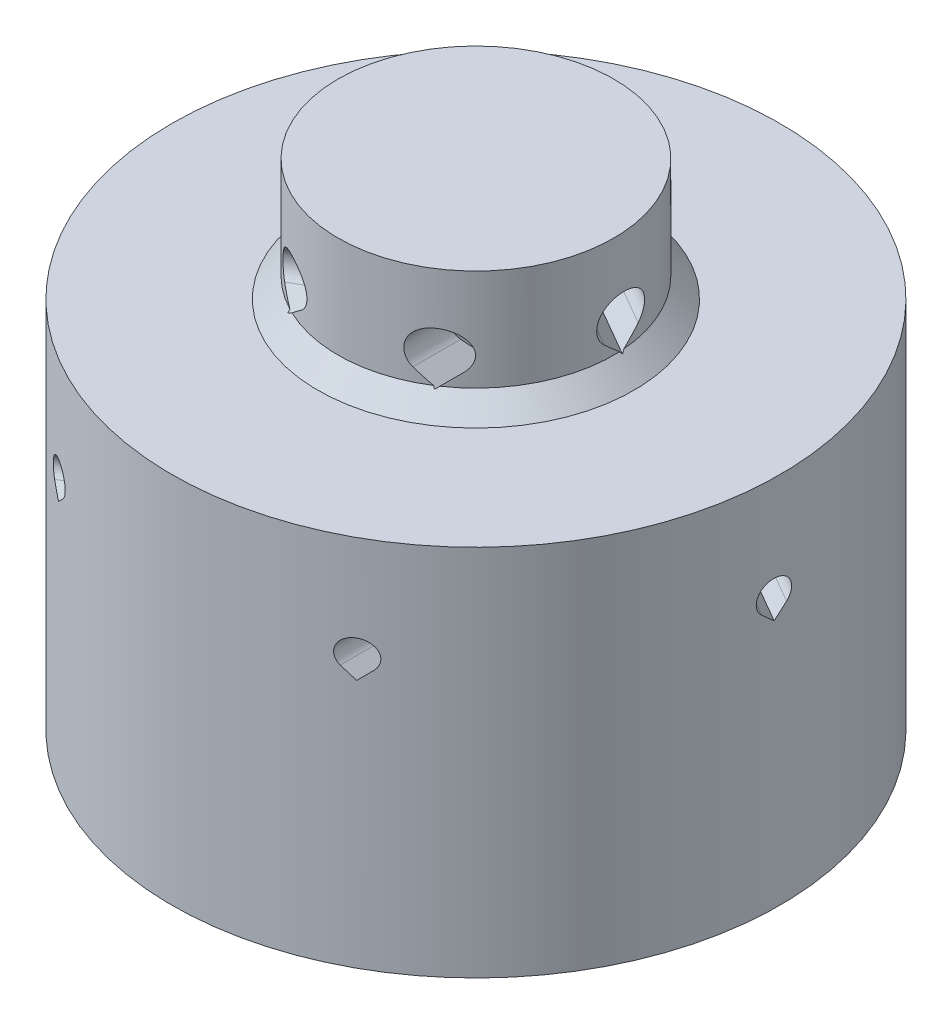
SolidWorks part; units mm, degrees
material "ASTM A36 Steel"
ref_plane "Front Plane" through (0, 0, 0) normal (0, 0, 1) x (1, 0, 0)
ref_plane "Top Plane" through (0, 0, 0) normal (0, 1, 0) x (1, 0, 0)
ref_plane "Right Plane" through (0, 0, 0) normal (1, 0, 0) x (0, 0, -1)
ref_axis "Axis1" through (0, 42.935, 0) along (0, -1, 0)
sketch "Sketch1" plane through (0, 0, 0) normal (0, 0, 1) x (1, 0, 0)
  line L1 (-5.3975, 0) -> (-5.3975, -3.9688)
  line L2 (-6.1912, -4.7625) -> (-11.9062, -4.7625)
  line L3 (-11.9062, -4.7625) -> (-11.9062, -7.1755)
  line L7 (-3.81, -1.5875) -> (-3.81, -13.0175)
  line L8 (-3.81, -13.0175) -> (-2.54, -14.2875)
  line L9 (-2.54, -14.2875) -> (-2.54, -16.8275)
  line L10 (-2.54, -16.8275) -> (-3.3337, -16.8275)
  line L11 (-3.3337, -16.8275) -> (-3.3337, -14.6163)
  line L12 (-3.3337, -14.6163) -> (-4.6037, -13.3463)
  line L13 (-4.6037, -13.3463) -> (-4.6037, -7.9375)
  line L14 (0, -1.5875) -> (0, -17.8202) construction
  line L15 (-4.6037, -7.9375) -> (-6.35, -7.9375)
  line L16 (-6.35, -7.9375) -> (-6.35, -7.1755)
  line L17 (-6.35, -7.1755) -> (-11.9062, -7.1755)
  line L19 (-5.3975, 0) -> (-4.445, 0)
  line L20 (-4.445, 0) -> (-4.445, -1.5875)
  line L21 (-4.445, -1.5875) -> (-3.81, -1.5875)
  line L22 (-6.1912, -4.7625) -> (-5.3975, -3.9688)
  point P10 (-6.35, -7.5565)
  dimension "D1" = 3.81
  dimension "D2" = 2.54
  dimension "D3" = 135
  dimension "D4" = 11.43
  dimension "D5" = 2.54
  dimension "D6" = 1.5875
  dimension "D7" = 3.175
  dimension "D8" = 0.7937
  dimension "D9" = 0.7937
  dimension "D10" = 0.762
  dimension "D11" = 1.5875
  dimension "D12" = 11.9062
  dimension "D13" = 3.175
  dimension "D14" = 135
  dimension "D15" = 6.35
  dimension "D16" = 4.445
  dimension "D17" = 0.7937
  dimension "D18" = 0.7937
revolve "Revolve1" add sketch "Sketch1" angle 360 about L14
sketch "Sketch2" plane through (0, 0, 0) normal (0, 0, 1) x (1, 0, 0)
  line L0 (-6.35, -7.9375) -> (-6.35, -14.2875)
  line L1 (-6.35, -7.1755) -> (-11.9062, -7.1755) construction
  line L2 (-6.35, -14.2875) -> (-4.445, -16.1925)
  line L3 (-4.445, -16.1925) -> (-4.445, -22.5425)
  line L4 (-4.445, -22.5425) -> (-6.35, -22.5425)
  line L5 (-6.35, -22.5425) -> (-6.35, -19.3675)
  line L7 (-11.9062, -7.1755) -> (-11.9062, -19.3675)
  line L8 (-10.3886, -19.3675) -> (-11.9062, -19.3675)
  line L9 (0, 42.935) -> (0, -67.065) construction
  line L10 (-6.35, -7.9375) -> (-6.35, -7.1755)
  line L11 (-6.35, -7.1755) -> (-11.9062, -7.1755)
  line L13 (0, -1.5875) -> (0, -17.8202) construction
  line L14 (-6.35, -19.3675) -> (-7.3152, -19.3675)
  line L15 (-7.3152, -19.3675) -> (-7.3152, -17.3863)
  line L16 (-7.3152, -17.3863) -> (-10.3886, -17.3863)
  line L17 (-10.3886, -17.3863) -> (-10.3886, -19.3675)
  point P2 (-11.8448, -7.1755)
  point P18 (-11.9062, -7.1755)
  dimension "D1" = 4.445
  dimension "D2" = 3.175
  dimension "D3" = 135
  dimension "D4" = 6.35
  dimension "D5" = 6.35
  dimension "D6" = 6.35
  dimension "D7" = 3.0734
  dimension "D8" = 1.9812
  dimension "D9" = 10.3886
revolve "Revolve2" add sketch "Sketch2" angle 360 about L14
sketch "Sketch3" plane through (0, 0, 0) normal (0, 0, 1) x (1, 0, 0)
  line L0 (-4.445, -1.5875) -> (0, -1.5875)
  line L1 (4.445, -1.5875) -> (-4.445, -1.5875) construction
  line L2 (0, -1.5875) -> (0, 0)
  line L3 (0, 0) -> (-4.445, 0)
  line L4 (-4.445, 0) -> (-4.445, -1.5875)
revolve "Revolve3" add sketch "Sketch3" angle 360 about L2
sketch "Sketch8" plane through (0, 0, 0) normal (0, 0, 1) x (1, 0, 0)
  line L0 (-2.9718, -4.0429) -> (-3.5645, -3.4502)
  line L1 (-2.3791, -3.4502) -> (-2.9718, -4.0429)
  line L2 (-2.9718, -2.8575) -> (-2.9718, -4.0429) construction
  line L3 (-3.81, -1.5875) -> (-3.81, -13.0175) construction
  line L4 (5.3975, 0) -> (-5.3975, 0) construction
  arc A0 (-3.5645, -3.4502) -> (-2.3791, -3.4502) centre (-2.9718, -2.8575) cw
  point P4 (-3.5416, -4.5666)
  point P5 (-3.81, -2.8575)
  point P6 (0, 0)
  point P7 (0, 0)
  dimension "D2" = 0.8382
  dimension "D1" = 90
  dimension "D3" = 2.8575
extrude "Cut-Extrude1" cut sketch "Sketch8" against normal through all
pattern_circular "CirPattern1" count 6 over 360 about axis through (0, 42.935, 0) along (0, -1, 0) of "Cut-Extrude1"
sketch "Sketch9" plane through (0, 0, 0) normal (0, 0, 1) x (1, 0, 0)
  line L0 (-5.7547, -9.6049) -> (-6.1756, -9.1839)
  line L1 (-5.3337, -9.1839) -> (-5.7547, -9.6049)
  line L2 (-5.7547, -9.6049) -> (-5.7547, -8.763) construction
  line L3 (-6.35, -7.9375) -> (-6.35, -14.2875) construction
  line L5 (-6.35, -7.1755) -> (-11.9062, -7.1755) construction
  arc A0 (-6.1756, -9.1839) -> (-5.3337, -9.1839) centre (-5.7547, -8.763) cw
  point P4 (-6.35, -8.763)
  point P5 (0, 0)
  dimension "D2" = 0.5953
  dimension "D1" = 90
  dimension "D3" = 1.5875
extrude "Cut-Extrude2" cut sketch "Sketch9" against normal through all
pattern_circular "CirPattern2" count 6 over 360 about axis through (0, 42.935, 0) along (0, -1, 0) of "Cut-Extrude2"
ref_axis "Axis2" through (13.0969, 0, 0) along (-1, 0, 0)
ref_axis "Axis3" through (0, 0, -13.0969) along (0, 0, 1)
equation "\".o625\"=0.0585896"
